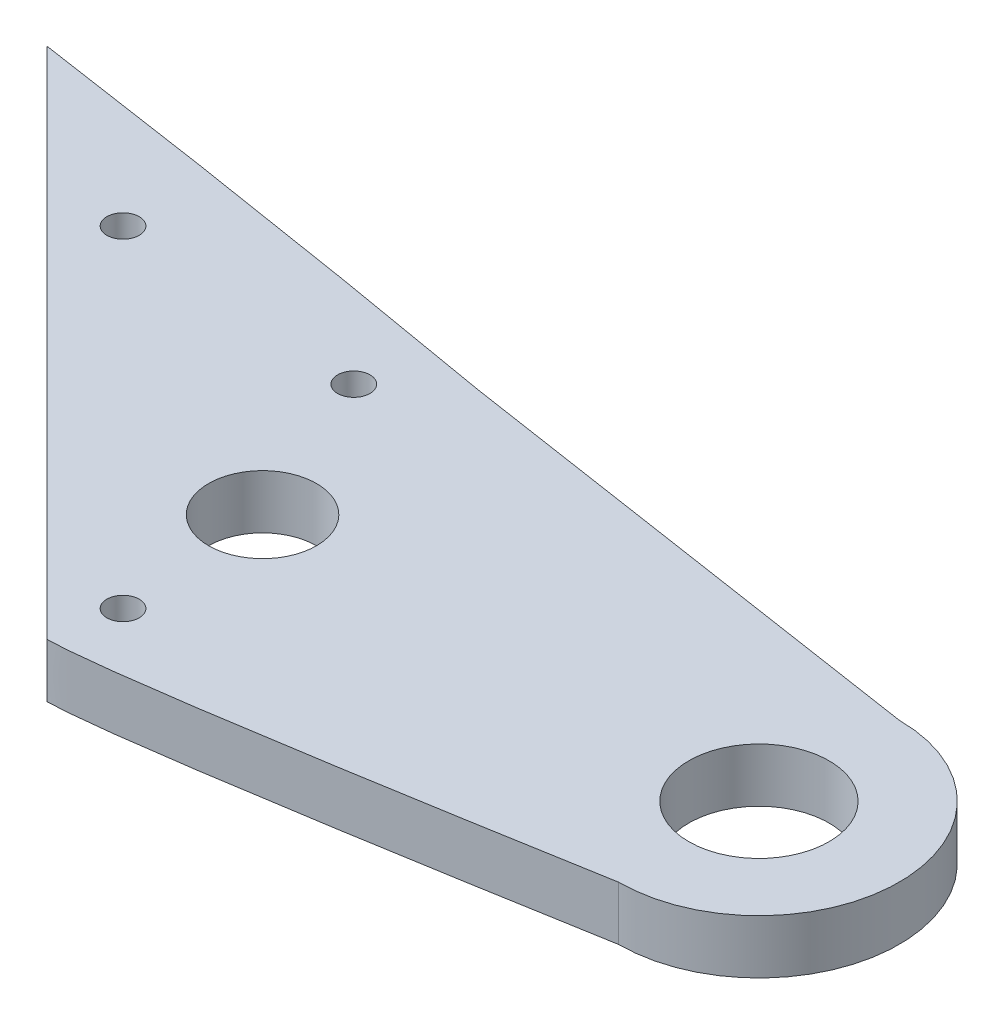
SolidWorks part; units mm, degrees
ref_plane "Front Plane" through (0, 0, 0) normal (0, 0, 1) x (1, 0, 0)
ref_plane "Top Plane" through (0, 0, 0) normal (0, 1, 0) x (1, 0, 0)
ref_plane "Right Plane" through (0, 0, 0) normal (1, 0, 0) x (0, 0, -1)
sketch "Sketch1" plane through (0, 0, 0) normal (0, 1, 0) x (1, 0, 0)
  line L0 (0, 0) -> (-300, 0) construction
  line L1 (0, 0) -> (46, 0) construction
  line L2 (-300, 0) -> (-300, 40) construction
  line L3 (-328.2843, 28.2843) -> (-271.7157, -28.2843) construction
  circle A0 centre (0, 0) radius 5
  circle A1 centre (46, 0) radius 6.5
  circle A2 centre (-300, 0) radius 40
  circle A3 centre (0, 0) radius 20
  circle A4 centre (46, 0) radius 13
  spline S0 degree 3 poles (-271.7157, -28.2843) (-189.2199, 54.2115) (-20, -20) (0, -20) knots 0 0 0 0 1 1 1 1
  spline S1 degree 3 poles (-328.2843, 28.2843) (-300, 56.5685) (-114.8731, 40.3783) (0, 20) knots 0 0 0 0 1 1 1 1
  spline S2 degree 2 poles (0, -20) (5.9085, -20) (46, -13) knots 0 0 0 1 1 1
  spline S3 degree 2 poles (0, 20) (0.0315, 20) (46, 13) knots 0 0 0 1 1 1
  dimension "D3" = 10
  dimension "D4" = 13
  dimension "D5" = 80
  dimension "D6" = 40
  dimension "D7" = 45
  dimension "D8" = 120
  dimension "D9" = 350
  dimension "D10" = 350
  dimension "D11" = 60
  dimension "D12" = 26
  dimension "D1" = 46
  dimension "D2" = 300
extrude "Boss-Extrude1" add sketch "Sketch1" along normal blind 20 and the other way blind 20 contours S1 A2 | S1 A2 S0 A3 | S3 A3 S0 A0 | S3 A3 S2 A4 | A4 A1 region at (-299.9271, 0, 0.2395) region at (-151.7179, 0, -19.1123) region at (-19.1932, 0, -3.0516) region at (26.0397, 0, 0.3418) region at (54.9324, 0, -8.9324)
ref_plane "Plane1" through (-121.7157, 0, -121.7157) normal (0.7071, 0, 0.7071) x (0, 1, 0)
sketch "Sketch3" plane through (-71.2994, 0, -172.132) normal (0.7071, 0, 0.7071) x (0.7071, 0, -0.7071)
  line L0 (-2.323, 174.4861) -> (-2.323, -69.6609) construction
  line L1 (-283.4315, 0) -> (16.5685, 0) construction
  line L2 (-283.4315, -20) -> (-85.4416, -20)
  line L3 (-283.4315, -20) -> (-283.4315, 20) construction
  line L6 (-283.4315, -20) -> (-283.4315, 20)
  line L7 (-323.4315, -20) -> (-283.4315, -20) construction
  line L8 (-283.4315, 20) -> (-323.4315, 20) construction
  line L9 (-283.4315, 20) -> (-85.4416, 20)
  spline S0 degree 3 poles (-283.4315, 20) (-184.8054, 3.4801) (-115.2658, 16.7576) (-85.4416, 20) knots 0 0 0 0 1 1 1 1
  spline S1 degree 3 poles (-283.4315, -20) (-184.8054, -3.4801) (-115.2658, -16.7576) (-85.4416, -20) knots 0 0 0 0 1 1 1 1
  dimension "D3" = 90
  dimension "D1" = 300
  dimension "D2" = 300
extrude "Cut-Extrude2" cut sketch "Sketch3" against normal through all and the other way through all contours S1 L2 | L9 S0 region at (-202.9789, -16.7688, -40.4526)
ref_plane "Plane2" through (0, 20, 0) normal (0, 1, 0) x (1, 0, 0)
sketch "Sketch4" plane through (0, 20, 0) normal (0, 1, 0) x (1, 0, 0)
  line L0 (-47.6102, 27.6102) -> (0, -20)
  line L1 (0, -20) -> (-373.5445, -70.3301)
  line L2 (-373.5445, -70.3301) -> (-354.3284, 116.9391)
  line L3 (-354.3284, 116.9391) -> (-47.6102, 27.6102)
extrude "Cut-Extrude3" cut sketch "Sketch4" against normal blind 50
sketch "Sketch5" plane through (0, 20, 0) normal (0, 1, 0) x (1, 0, 0)
  line L0 (-57.2758, 36.8453) -> (76.2453, 18.3817)
  line L1 (76.2453, 18.3817) -> (61.0857, -35.26)
  line L2 (61.0857, -35.26) -> (-58.6362, -33.3165)
  line L3 (-58.6362, -33.3165) -> (-57.2758, 36.8453)
extrude "Cut-Extrude4" cut sketch "Sketch5" against normal blind 35
sketch "Sketch6" plane through (0, -20, 0) normal (0, -1, 0) x (-1, 0, 0)
  circle A1 centre (-1.0699, -13.9989) radius 1.5
  circle A2 centre (6.2432, 14.6972) radius 1.5
  circle A3 centre (29.628, 16.6991) radius 1.5
  dimension "D1" = 3
extrude "Cut-Extrude5" cut sketch "Sketch6" against normal blind 10
